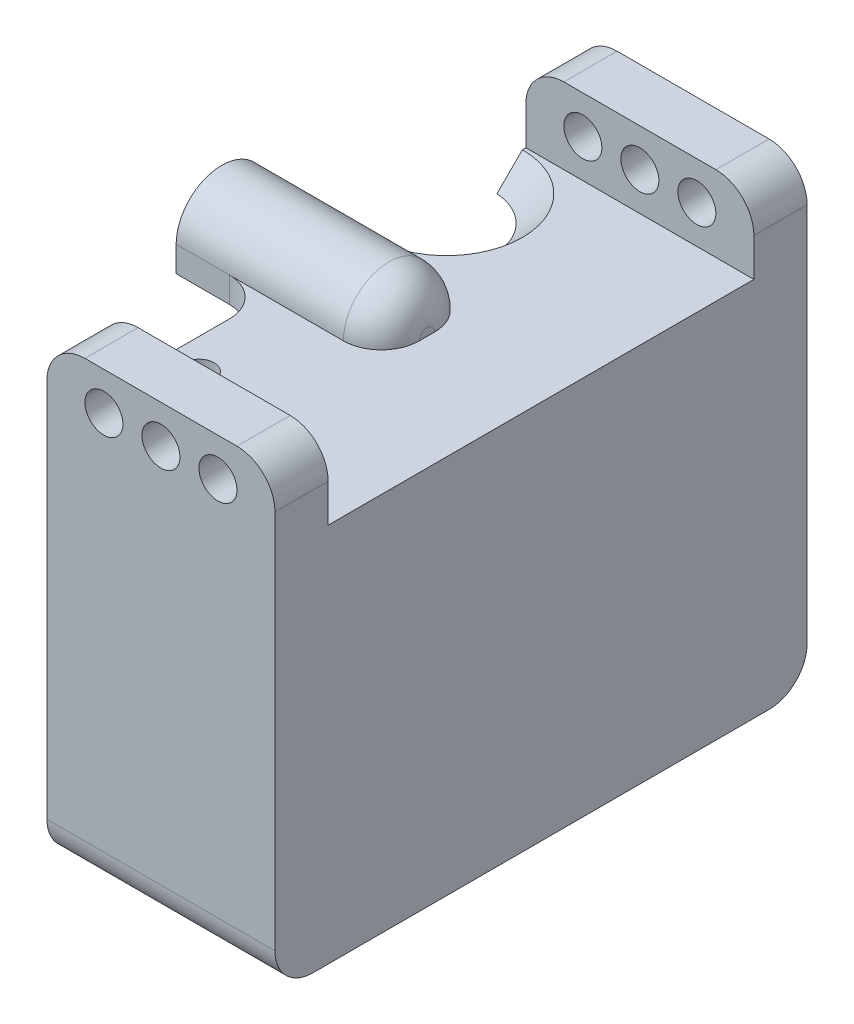
SolidWorks part; units mm, degrees
note: The reader was unsure of these and kept them because the rebuilt part matched: shared geometry of "Sketch8<2>".
ref_plane "Front Plane" through (0, 0, 0) normal (0, 0, 1) x (1, 0, 0)
ref_plane "Top Plane" through (0, 0, 0) normal (0, 1, 0) x (1, 0, 0)
ref_plane "Right Plane" through (0, 0, 0) normal (1, 0, 0) x (0, 0, -1)
sketch "Sketch1" plane through (0, 0, 0) normal (1, 0, 0) x (0, 0, -1)
  line L1 (-35, -25) -> (35, -25)
  line L2 (-35, -25) -> (-35, 25)
  line L3 (-35, 25) -> (35, 25)
  line L4 (35, -25) -> (35, 25)
  line L5 (-35, -25) -> (35, 25) construction
  line L6 (-35, 25) -> (35, -25) construction
  point P0 (0, 0)
  dimension "D1" = 50
  dimension "D2" = 70
extrude "Boss-Extrude1" add sketch "Sketch1" along normal blind 30
fillet "Fillet1" [suppressed] radius 3
sketch "Sketch2" plane through (0, 0, 0) normal (-1, 0, 0) x (0, 0, 1)
  line L1 (-30.55, -21.65) -> (30.55, -21.65)
  line L2 (-30.55, -21.65) -> (-30.55, 21.65)
  line L3 (-30.55, 21.65) -> (30.55, 21.65)
  line L4 (30.55, -21.65) -> (30.55, 21.65)
  line L5 (-30.55, -21.65) -> (30.55, 21.65) construction
  line L6 (-30.55, 21.65) -> (30.55, -21.65) construction
  point P0 (0, 0)
  dimension "D1" = 61.1
  dimension "D2" = 43.3
extrude "Cut-Extrude1" cut sketch "Sketch2" against normal offset from surface 2 draft 2
sketch "Sketch3" plane through (0, 0, 0) normal (1, 0, 0) x (0, 0, -1)
  line L0 (-35, 25) -> (-35, -25) construction
  line L1 (-35, 21.65) -> (-28, 21.65)
  line L2 (-35, 21.65) -> (-35, 35)
  line L3 (-35, 35) -> (-28, 35)
  line L4 (-28, 21.65) -> (-28, 35)
  line L5 (0, 0) -> (0, 29.1686) construction
  line L6 (-30.55, 21.65) -> (30.55, 21.65) construction
  line L7 (28, 21.65) -> (28, 35)
  line L8 (35, 35) -> (28, 35)
  line L9 (35, 21.65) -> (35, 35)
  line L10 (35, 21.65) -> (28, 21.65)
  dimension "D1" = 7
  dimension "D2" = 35
extrude "Hang tabs" add sketch "Sketch3" along normal up to surface (30 mm away) up to face at (30, 0, 0)
sketch "Sketch4" plane through (0, 0, 0) normal (-1, 0, 0) x (0, 0, 1)
  line L0 (-28, 25) -> (28, 25) construction
  line L1 (35, -25) -> (-35, -25) construction
  line L4 (30.55, 21.65) -> (-30.55, 21.65) construction
  line L6 (-6, 25) -> (-6, 21.65)
  line L7 (-6, 21.65) -> (6, 21.65)
  line L8 (6, 25) -> (6, 21.65)
  line L9 (-30.55, -21.65) -> (30.55, -21.65) construction
  line L10 (-6, -21.65) -> (6, -21.65)
  line L11 (-6, -21.65) -> (-6, -25)
  line L13 (6, -21.65) -> (6, -25)
  arc A0 (-6, 25) -> (6, 25) centre (0, 25) cw
  arc A1 (6, -25) -> (-6, -25) centre (0, -25) cw
  dimension "D1" = 6
extrude "Boss-Extrude3" add sketch "Sketch4" against normal blind 15 and the other way blind 12
sketch "Sketch5" plane through (-12, 0, 0) normal (-1, 0, 0) x (0, 0, 1)
  circle A0 centre (0, 25) radius 1.5
  circle A1 centre (0, -25) radius 1.5
  dimension "D1" = 3
  dimension "D2" = 3
extrude "Cut-Extrude2" cut sketch "Sketch5" against normal blind 15
sketch "Sketch6" plane through (0, 0, 0) normal (0, 1, 0) x (1, 0, 0)
  line L0 (0, 28) -> (0, 6) construction
  circle A0 centre (0, 17.55) radius 5
  dimension "D1" = 10
  dimension "D2" = 13
extrude "Cut-Extrude3" cut sketch "Sketch6" along normal through all
sketch "Sketch7" plane through (0, 0, 0) normal (0, 1, 0) x (1, 0, 0)
  line L0 (4, -19) -> (4, -23) construction
  line L1 (6, -19) -> (6, -23)
  line L2 (2, -19) -> (2, -23)
  line L3 (30, -28) -> (0, -28) construction
  line L4 (0, -6) -> (0, -28) construction
  arc A0 (6, -19) -> (2, -19) centre (4, -19) ccw
  arc A1 (2, -23) -> (6, -23) centre (4, -23) ccw
  point P2 (4, -21)
  dimension "D1" = 4
  dimension "D2" = 4
  dimension "D3" = 7
  dimension "D4" = 4
extrude "Cut-Extrude4" cut sketch "Sketch7" along normal through all
sketch "Sketch8" plane through (0, 0, 0) normal (0, 0, 1) x (1, 0, 0)
  line L0 (0, 30) -> (30, 30) construction
  line L1 (0, 35) -> (0, -25) construction
  line L2 (30, 35) -> (30, -25) construction
  line L3 (30, 25) -> (0, 25) construction
  circle A0 centre (15, 30) radius 2.5
  circle A1 centre (22.5, 30) radius 2.5
  circle A2 centre (7.5, 30) radius 2.5
  dimension "D2" = 5
  dimension "D1" = 5
  dimension "D3" = 7.5
  dimension "D4" = 7.5
extrude "Cut-Extrude5" cut sketch "Sketch8" against normal through all from surface at -28 starting at face at (15, 30, -28)
extrude "Cut-Extrude6" cut sketch "Sketch8<2>" along normal through all from surface at 28 starting at face at (15, 30, 28)
sketch "Sketch8<2>" plane through (0, 0, 0) normal (0, 0, 1) x (1, 0, 0) same geometry as "Sketch8"
fillet "Fillet2" radius 5 4 edges at (0, 35, -31.5) (0, 35, 31.5) (30, 35, -31.5) (30, 35, 31.5)
fillet "Fillet3" radius 5 2 edges at (15, -31, 0) (15, 31, 0)
chamfer "Chamfer1" distance 5 angle 45 1 edges at (5, 25, -17.55)
fillet "Fillet4" radius 5 2 edges at (15, -25, 35) (15, -25, -35)
sketch "Sketch9" plane through (0, 0, 0) normal (-1, 0, 0) x (0, 0, 1)
  line L0 (0, 0) -> (0, -38.3) construction
  line L1 (30.55, 21.65) -> (6, 21.65) construction
  line L2 (-7.5, 16.65) -> (7.5, 16.65)
  line L3 (-7.5, 16.65) -> (-7.5, 21.65)
  line L4 (-7.5, 21.65) -> (7.5, 21.65)
  line L5 (7.5, 16.65) -> (7.5, 21.65)
  line L6 (-7.5, 16.65) -> (7.5, 21.65) construction
  line L7 (-7.5, 21.65) -> (7.5, 16.65) construction
  line L8 (-7.5, -16.65) -> (7.5, -16.65)
  line L9 (-7.5, -16.65) -> (-7.5, -21.65)
  line L10 (-7.5, -21.65) -> (7.5, -21.65)
  line L11 (7.5, -16.65) -> (7.5, -21.65)
  line L12 (-7.5, -16.65) -> (7.5, -21.65) construction
  line L13 (-7.5, -21.65) -> (7.5, -16.65) construction
  line L14 (-30.55, -21.65) -> (-6, -21.65) construction
  point P3 (0, 19.15)
  point P8 (0, -19.15)
  dimension "D1" = 5
  dimension "D2" = 15
  dimension "D3" = 5
  dimension "D4" = 5
extrude "Boss-Extrude4" add sketch "Sketch9" against normal up to surface (10.5 mm away) from offset 17.5 up to face at (28, 0, 0) offset against normal yes
fillet "Fillet5" radius 5 3 edges at (0, 23.325, 6) (0, -23.325, 6) (0, -23.325, -6)
fillet "Fillet6" radius 1 10 edges at (28, 20.6722, -18.5361) (28, 0, -29.5722) (28, -20.6722, -18.5361) (28, -20.6722, 18.5361) (28, 0, 29.5722) (28, 20.6722, 18.5361) (14, 21.1611, 30.0611) (14, -21.1611, 30.0611) (14, -21.1611, -30.0611) (14, 21.1611, -30.0611)
